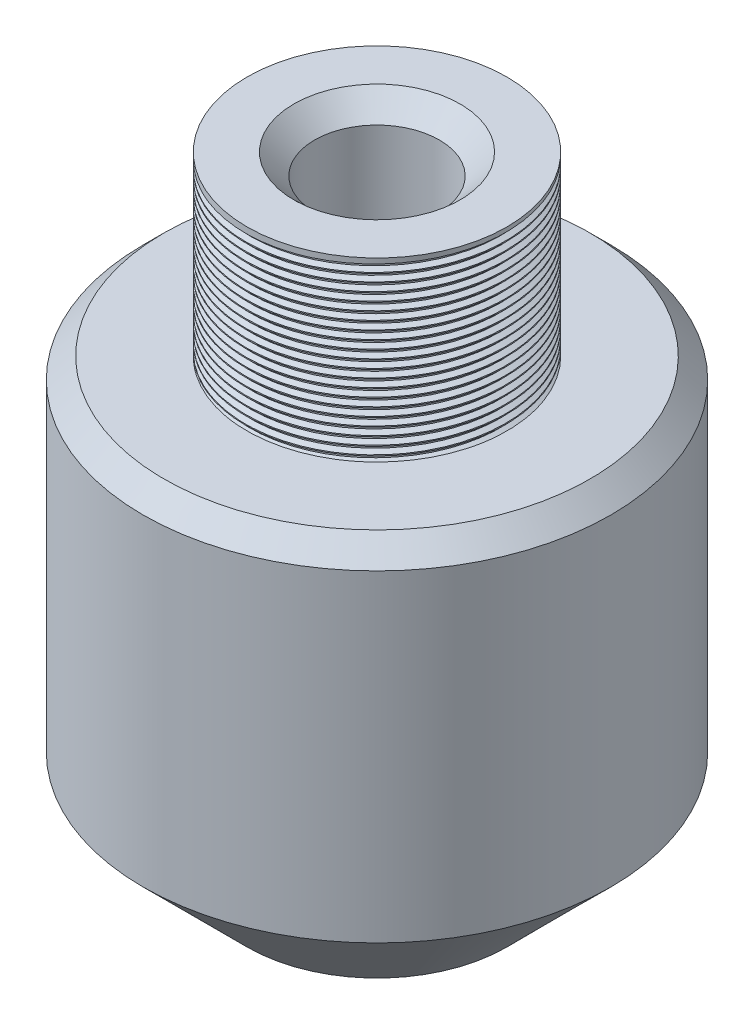
SolidWorks part; units mm, degrees
ref_plane "Спереди" through (0, 0, 0) normal (0, 0, 1) x (1, 0, 0)
ref_plane "Сверху" through (0, 0, 0) normal (0, 1, 0) x (1, 0, 0)
ref_plane "Справа" through (0, 0, 0) normal (1, 0, 0) x (0, 0, -1)
sketch "Эскиз1" plane through (0, 0, 0) normal (0, 0, 1) x (1, 0, 0)
  line L4 (6, -28) -> (6, 28)
  line L5 (0, 0) -> (0, -22.2461) construction
  line L6 (12.5, 13) -> (20.5, 13)
  line L7 (22.5, 11) -> (22.5, -20)
  line L10 (8, -30) -> (6, -28)
  line L11 (22.5, -20) -> (12.5, -30)
  line L12 (12.5, -30) -> (8, -30)
  line L13 (20.5, 13) -> (22.5, 11)
  line L14 (12.5, 13) -> (12.5, 30)
  line L17 (6, 28) -> (8, 30)
  line L18 (8, 30) -> (12.5, 30)
  point P10 (6, 0)
  dimension "D1" = 12
  dimension "D2" = 45
  dimension "D3" = 45
  dimension "D4" = 17
  dimension "D5" = 45
  dimension "D6" = 2
  dimension "D7" = 45
  dimension "D8" = 10
  dimension "D9" = 2
  dimension "D10" = 45
  dimension "D11" = 2
  dimension "D12" = 60
  dimension "D13" = 25
revolve "Повернуть1" add sketch "Эскиз1" angle 360 about L5
thread "Резьба1" pitch 0.8 method cut profile "Профиль резьбы1" start angle 0, offset 0, length 17, pitch 0.8, diameter 25
ref_plane "Плоскость1" through (-12.5, 30, 0) normal (0, 0, 1) x (-1, 0, 0)
sketch "Профиль резьбы1" plane through (-12.5, 30, 0) normal (0, 0, 1) x (-1, 0, 0)
  line L0 (0, 0) -> (0, 0.8) construction
  line L11 (0, 0) -> (0, 0.7)
  line L12 (0, 0.7) -> (-0.433, 0.45)
  line L13 (-0.433, 0.45) -> (-0.433, 0.25)
  line L15 (-0.433, 0.25) -> (0, 0)
  line L17 (-0.433, 0.35) -> (0, 0.35) construction
  point P2 (0, 0)
  dimension "Pitch" = 0.8
  dimension "Profile_Angle" = 60
  dimension "Profile_Land" = 0.2
  dimension "Profile_Height" = 0.433
